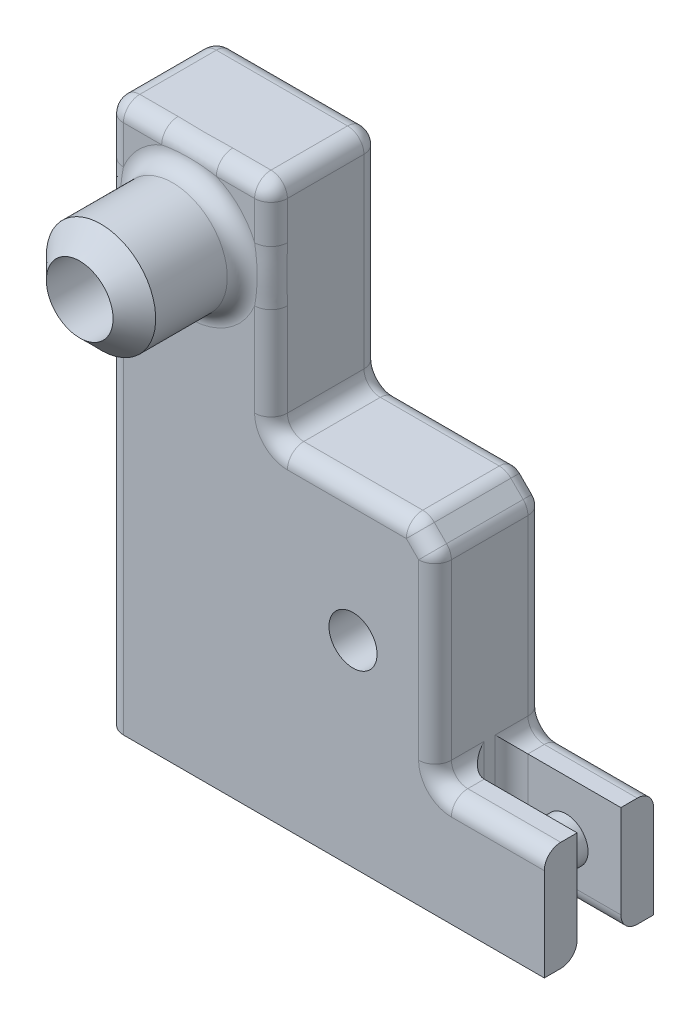
SolidWorks part; units mm, degrees
ref_plane "Front Plane" through (0, 0, 0) normal (0, 0, 1) x (1, 0, 0)
ref_plane "Top Plane" through (0, 0, 0) normal (0, 1, 0) x (1, 0, 0)
ref_plane "Right Plane" through (0, 0, 0) normal (1, 0, 0) x (0, 0, -1)
sketch "Sketch1" plane through (0, 0, 0) normal (0, 0, 1) x (1, 0, 0)
  line L0 (-15, 0) -> (-15, 50)
  line L1 (-15, 50) -> (0, 50)
  line L2 (0, 50) -> (0, 30)
  line L5 (0, 30) -> (15, 30)
  line L6 (15, 30) -> (15, 0)
  line L12 (-15, 0) -> (15, 0)
  circle A0 centre (-7.5, 42.5) radius 3.05
  circle A1 centre (7.5, 18) radius 2.2
  point P8 (0, 0)
  point P12 (-7.5, 50)
  point P16 (7.5, 30)
  dimension "D7" = 6.1
  dimension "D9" = 4.4
  dimension "D1" = 50
  dimension "D2" = 15
  dimension "D3" = 30
  dimension "D6" = 20
  dimension "D8" = 7.5
  dimension "D10" = 12
extrude "Boss-Extrude1" add sketch "Sketch1" along normal blind 6 and the other way blind 4
sketch "Sketch2" plane through (15, 0, 0) normal (1, 0, 0) x (0, 0, -1)
  line L0 (-6, 0) -> (4, 0) construction
  line L1 (-6, 0) -> (-6, 30) construction
  circle A0 centre (-1, 5) radius 2.5
  dimension "D1" = 5
  dimension "D2" = 5
  dimension "D3" = 5
extrude "Boss-Extrude2" [suppressed] add sketch "Sketch2" along normal blind 6
sketch "Sketch3" [suppressed] plane through (21, 0, 0) normal (1, 0, 0) x (0, 0, -1)
  circle A0 centre (-1, 5) radius 4.5
  circle A1 centre (-1, 5) radius 2.5
  circle A2 centre (-1, 5) radius 2.5 construction
  dimension "D1" = 0
  dimension "D2" = 2
extrude "Boss-Extrude3" [suppressed] add sketch "Sketch3" along normal blind 2
ref_plane "Plane1" through (0, 0, -4) normal (0, 0, -1) x (-1, 0, 0)
sketch "Sketch4" plane through (0, 0, -4) normal (0, 0, -1) x (-1, 0, 0)
  line L0 (-15, 0) -> (-15, 10)
  line L1 (-15, 0) -> (-25, 0)
  line L2 (-15, 10) -> (-25, 10)
  line L3 (-25, 0) -> (-25, 10)
  line L4 (-15, 0) -> (-15, 30) construction
  dimension "D1" = 10
  dimension "D2" = 10
extrude "Boss-Extrude4" add sketch "Sketch4" against normal blind 10
sketch "Sketch5" plane through (25, 0, 0) normal (1, 0, 0) x (0, 0, -1)
  line L0 (-3, 10) -> (1, 10)
  line L1 (-3, 10) -> (-3, 0)
  line L2 (1, 10) -> (1, 0)
  line L3 (-3, 0) -> (1, 0)
  line L4 (-6, 10) -> (4, 10) construction
  line L5 (-6, 0) -> (4, 0) construction
  line L7 (-6, 10) -> (4, 10) construction
  point P8 (-1, 10)
  dimension "D1" = 4
extrude "Cut-Extrude1" cut sketch "Sketch5" against normal up to surface (10 mm away) up to face at (15, 20, 1)
sketch "Sketch6" plane through (0, 0, -1) normal (0, 0, 1) x (1, 0, 0)
  line L0 (25, 10) -> (25, 0) construction
  line L1 (15, 10) -> (25, 10) construction
  circle A0 centre (20, 5) radius 2
  dimension "D1" = 4
  dimension "D2" = 5
  dimension "D3" = 5
extrude "Boss-Extrude5" add sketch "Sketch6" along normal up to next
fillet "Fillet1" [suppressed] radius 2
chamfer "Chamfer1" distance 2 angle 45 1 edges at (15, 30, 1)
sketch "Sketch25" plane through (0, 0, -4) normal (0, 0, 1) x (1, 0, 0)
  circle A2 centre (7.5, 18) radius 5.5
  circle A3 centre (7.5, 18) radius 5.5
  dimension "D1" = 3.3
extrude "Cut-Extrude9" cut sketch "Sketch25" along normal blind 3
ref_plane "Plane4" through (-7.5, 0, 0) normal (1, 0, 0) x (0, 0, -1)
sketch "Sketch26" plane through (-7.5, 0, 0) normal (1, 0, 0) x (0, 0, -1)
  line L0 (-6, 42.5) -> (-16, 42.5)
  line L1 (-6, 30) -> (-6, 50) construction
  line L2 (-16, 42.5) -> (-16, 45.55)
  line L3 (-16, 45.55) -> (-14.05, 47.5)
  line L4 (-14.05, 47.5) -> (-6, 47.5)
  line L5 (-6, 47.5) -> (-6, 42.5)
  line L6 (4, 50) -> (-6, 50) construction
  dimension "D1" = 7.5
  dimension "D2" = 10
  dimension "D3" = 5
  dimension "D4" = 135
  dimension "D5" = 3.05
revolve "Revolve2" add sketch "Sketch26" angle 360 about L0
sketch "Sketch27" plane through (0, 0, 16) normal (0, 0, 1) x (1, 0, 0)
  circle A1 centre (-7.5, 42.5) radius 3.05
  circle A2 centre (-7.5, 42.5) radius 3.05
  dimension "D1" = 0
extrude "Cut-Extrude10" cut sketch "Sketch27" against normal up to next
fillet "Fillet6" radius 1.5 1 edges at (-12.5, 42.5, 6)
fillet "Fillet7" radius 1.5 26 edges at (20, 10, -4) (20, 0, -1) (20, 0, 3) (20, 10, 6) (15, 10, -2.5) (15, 5, -1) (15, 0, 1) (15, 5, 3) (15, 10, 4.5) (15, 19, 6) (15, 19, -4) (15, 28, 1) (14, 29, 6) (14, 29, -4) (0, 30, 1) (6.5, 30, -4) (13, 30, 1) (6.5, 30, 6) (0, 40, -4) (-15, 25, -4) (-7.5, 50, -4) (-15, 50, 1) (0, 50, 1) (0, 40, 6) (-7.5, 50, 6) (-15, 25, 6)
sketch "Sketch7" [suppressed] plane through (0, 0, 0) normal (0, -1, 0) x (1, 0, 0)
  line L0 (-24.75, -4) -> (24.75, -4) construction
  line L1 (25, 11.5) -> (-15, 11.5) construction
  line L2 (25, 11.5) -> (25, -4) construction
  line L3 (25, -4) -> (-15, -4) construction
  line L4 (-15, 11.5) -> (-15, -4) construction
  line L5 (-15, 4.5) -> (-15, -2.5) construction
  line L12 (30, -4) -> (-20, -4)
  line L35 (-20, -4) -> (-20, 16.5)
  line L36 (-20, 16.5) -> (30, 16.5)
  line L37 (30, 16.5) -> (30, -4)
  line L39 (-13.5, 6) -> (25, 6) construction
  line L40 (25, -2.5) -> (25, -4) construction
  dimension "D2" = 5
  dimension "D1" = 5.5
  dimension "D3" = 5
  dimension "D4" = 5
